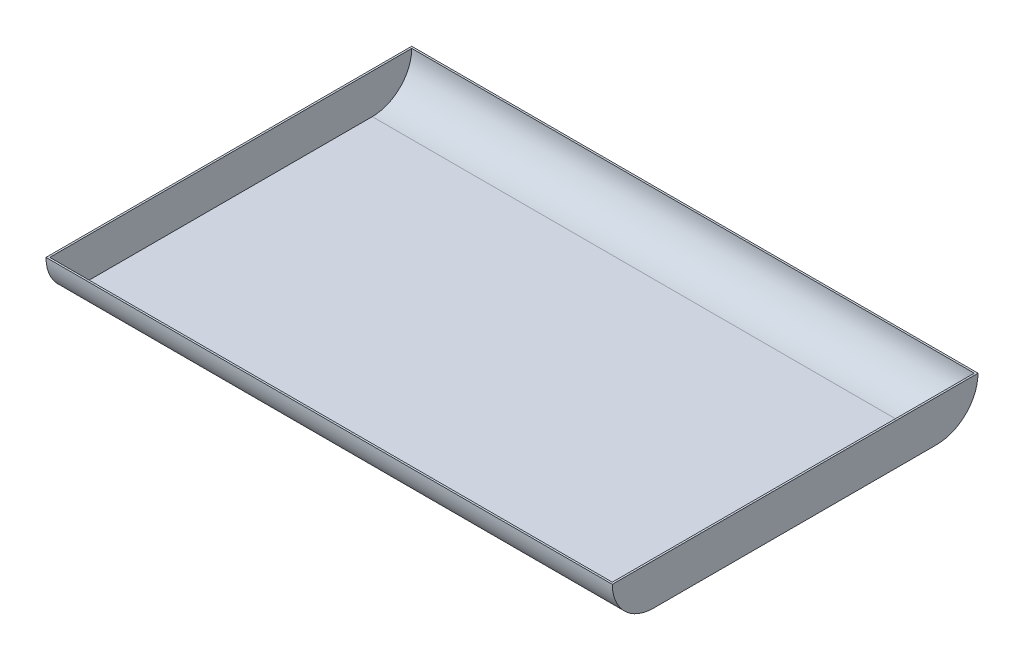
SolidWorks part; units mm, degrees
ref_plane "Front Plane" through (0, 0, 0) normal (0, 0, 1) x (1, 0, 0)
ref_plane "Top Plane" through (0, 0, 0) normal (0, 1, 0) x (1, 0, 0)
ref_plane "Right Plane" through (0, 0, 0) normal (1, 0, 0) x (0, 0, -1)
sketch "Sketch1" plane through (0, 0, 0) normal (1, 0, 0) x (0, 0, -1)
  line L0 (-152.4, 0) -> (152.4, 0)
  line L1 (-196.85, 44.45) -> (196.85, 44.45)
  line L2 (0, 0) -> (0, 113.2403) construction
  arc A0 (-152.4, 0) -> (-196.85, 44.45) centre (-152.4, 44.45) cw
  arc A1 (152.4, 0) -> (196.85, 44.45) centre (152.4, 44.45) ccw
  point P9 (0, 44.45)
  dimension "D3" = 44.45
  dimension "D1" = 304.8
  dimension "D2" = 152.4
extrude "Boss-Extrude1" add sketch "Sketch1" along normal blind 304.8 and the other way blind 304.8 contours L1 A1 L0 A0
shell "Shell1" thickness 2 removed face at (0, 44.45, 0)
